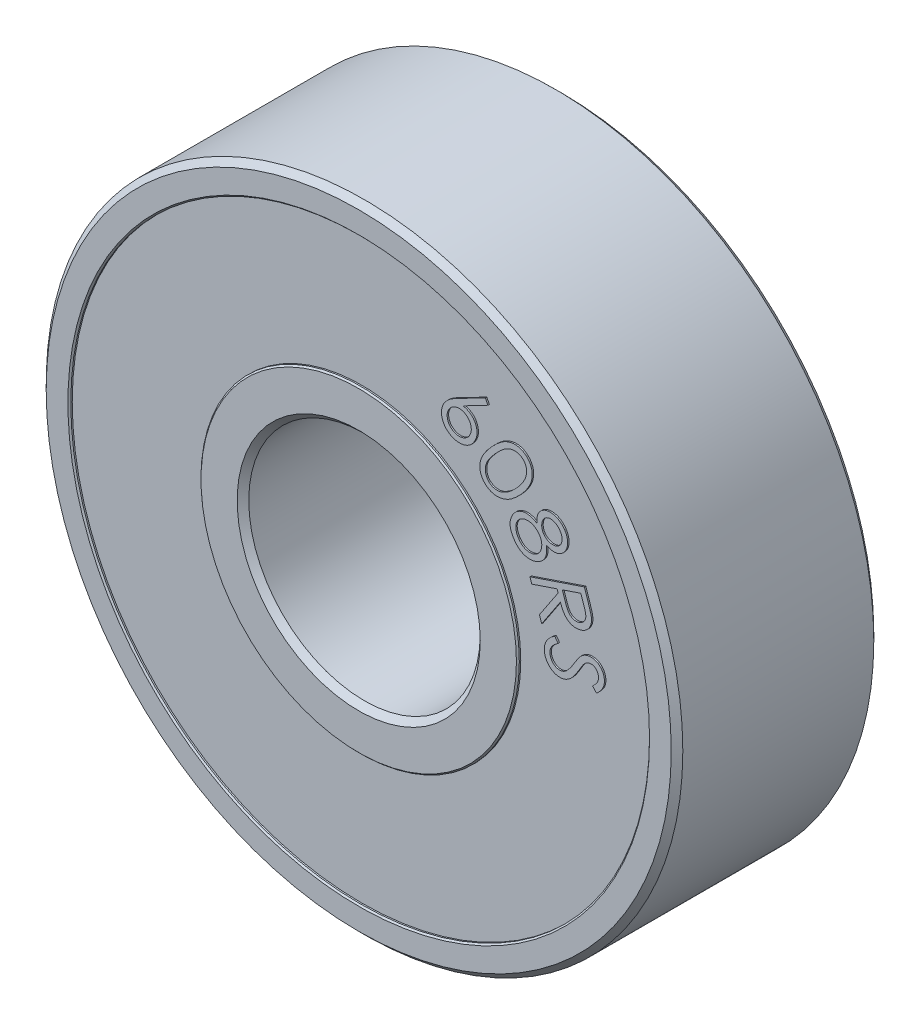
SolidWorks part; units mm, degrees
ref_plane "Front Plane" through (0, 0, 0) normal (0, 0, 1) x (1, 0, 0)
ref_plane "Top Plane" through (0, 0, 0) normal (0, 1, 0) x (1, 0, 0)
ref_plane "Right Plane" through (0, 0, 0) normal (1, 0, 0) x (0, 0, -1)
sketch "Sketch1" plane through (0, 0, 0) normal (0, 0, 1) x (1, 0, 0)
  circle A0 centre (0, 0) radius 11
  circle A1 centre (0, 0) radius 4
extrude "Boss-Extrude1" add sketch "Sketch1" along normal blind 7
sketch "Sketch2" plane through (0, 0, 7) normal (0, 0, 1) x (1, 0, 0)
  circle A0 centre (0, 0) radius 5.5
  circle A1 centre (0, 0) radius 10
extrude "Cut-Extrude1" cut sketch "Sketch2" against normal blind 0.1
extrude "Cut-Extrude2" cut sketch "Sketch2<2>" against normal blind 0.1 from offset 6.9 offset against normal yes
sketch "Sketch2<2>" plane through (0, 0, 7) normal (0, 0, 1) x (1, 0, 0) same geometry as "Sketch2"
chamfer "Chamfer1" distance 0.2 angle 45 4 edges at (4, 0, 0) (4, 0, 7) (11, 0, 7) (11, 0, 0)
chamfer "Chamfer2" distance 0.05 angle 45 4 edges at (5.5, 0, 7) (10, 0, 7) (10, 0, 0) (5.5, 0, 0)
sketch "Sketch3" plane through (0, 0, 0.1) normal (0, 0, -1) x (-1, 0, 0)
  circle A0 centre (0, 0) radius 6.5 construction
  text T0 "608RS" font "Century Gothic" height 2
extrude "Boss-Extrude2" add sketch "Sketch3" along normal blind 0.05
sketch "Sketch4" plane through (0, 0, 6.9) normal (0, 0, 1) x (1, 0, 0)
  circle A0 centre (0, 0) radius 6.5 construction
  text T0 "608RS" font "Century Gothic" height 2
extrude "Boss-Extrude3" add sketch "Sketch4" along normal blind 0.05
